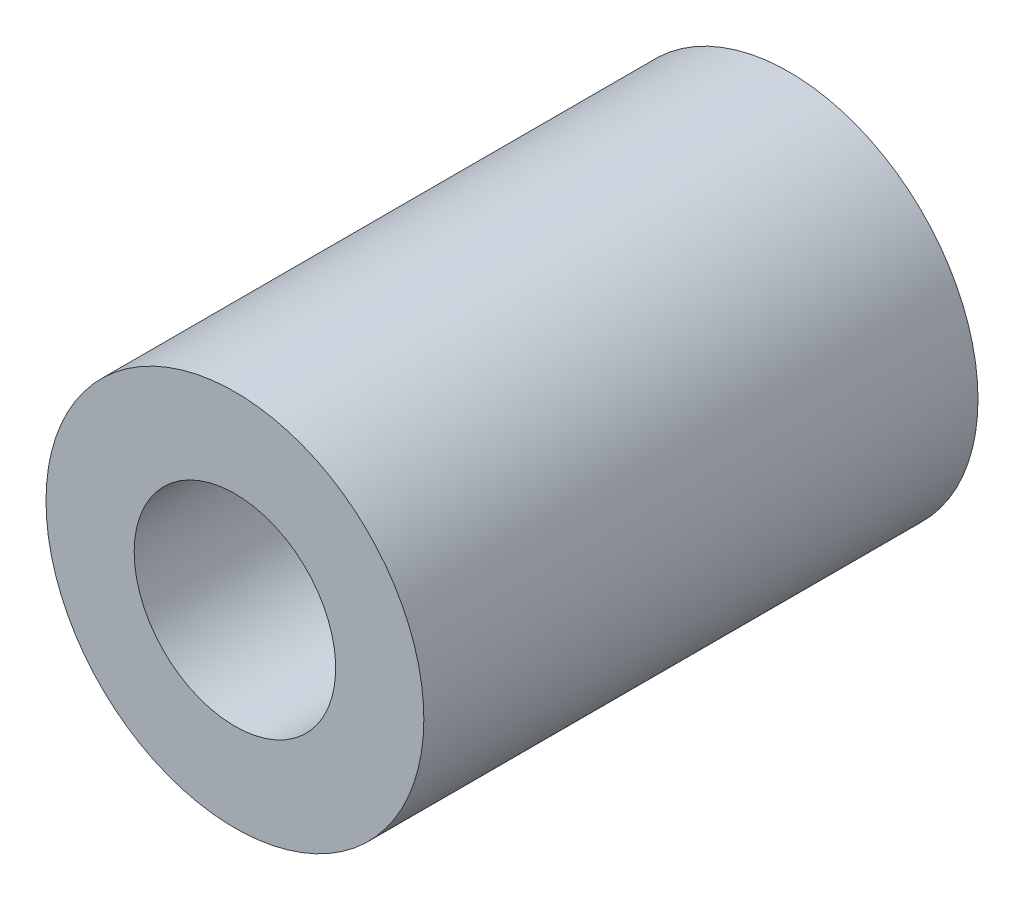
SolidWorks part; units mm, degrees
ref_plane "Front Plane" through (0, 0, 0) normal (0, 0, 1) x (1, 0, 0)
ref_plane "Top Plane" through (0, 0, 0) normal (0, 1, 0) x (1, 0, 0)
ref_plane "Right Plane" through (0, 0, 0) normal (1, 0, 0) x (0, 0, -1)
sketch "Sketch1" plane through (0, 0, 0) normal (0, 0, 1) x (1, 0, 0)
  circle A0 centre (0, 0) radius 7.5
extrude "Boss-Extrude1" add sketch "Sketch1" against normal up to surface (22 mm away)
sketch "Sketch2" plane through (0, 0, 0) normal (0, 0, 1) x (1, 0, 0)
  circle A0 centre (0, 0) radius 10
sketch "Sketch9" plane through (0, 0, -22) normal (0, 0, -1) x (-1, 0, 0)
  circle A0 centre (0, 0) radius 4
extrude "Cut-Extrude1" cut sketch "Sketch9" against normal through all
